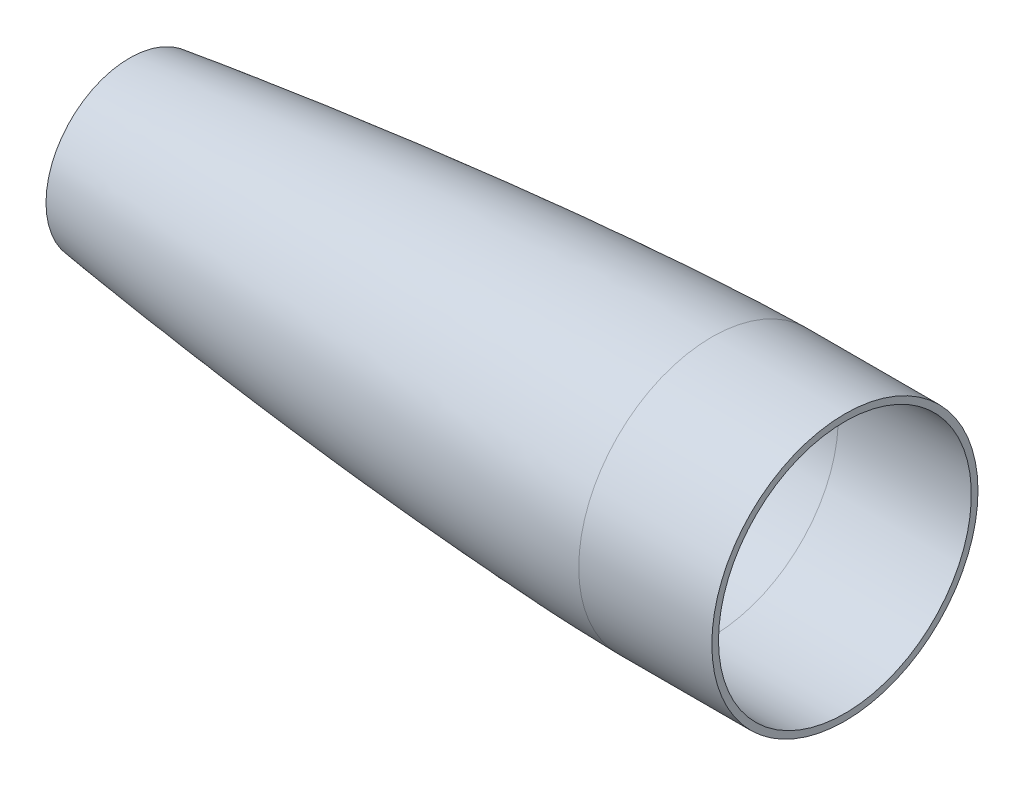
SolidWorks part; units mm, degrees
ref_plane "Front Plane" through (0, 0, 0) normal (0, 0, 1) x (1, 0, 0)
ref_plane "Top Plane" through (0, 0, 0) normal (0, 1, 0) x (1, 0, 0)
ref_plane "Right Plane" through (0, 0, 0) normal (1, 0, 0) x (0, 0, -1)
curve "Curve1"
  spline degree 3 poles (0, 0, 0) (0.3239, 0.2563, 0) (0.9404, 0.7441, 0) (1.9928, 1.2129, 0) (2.9928, 1.6503, 0) (3.9962, 2.0429, 0) (4.997, 2.4136, 0) (5.9977, 2.765, 0) (6.9982, 3.102, 0) (7.9985, 3.4266, 0) (8.9987, 3.7409, 0) (9.9989, 4.0463, 0) (10.999, 4.3437, 0) (11.9992, 4.6341, 0) (12.9993, 4.9182, 0) (13.9993, 5.1965, 0) (14.9994, 5.4695, 0) (15.9994, 5.7378, 0) (16.9995, 6.0015, 0) (17.9995, 6.261, 0) (18.9996, 6.5167, 0) (19.9996, 6.7687, 0) (20.9996, 7.0173, 0) (21.9996, 7.2626, 0) (22.9997, 7.5048, 0) (23.9997, 7.7441, 0) (24.9997, 7.9806, 0) (25.9997, 8.2145, 0) (26.9997, 8.4458, 0) (27.9997, 8.6747, 0) (28.9998, 8.9012, 0) (29.9998, 9.1256, 0) (30.9998, 9.3477, 0) (31.9998, 9.5678, 0) (32.9998, 9.7859, 0) (33.9998, 10.0021, 0) (34.9998, 10.2164, 0) (35.9998, 10.4289, 0) (36.9998, 10.6396, 0) (37.9998, 10.8486, 0) (38.9998, 11.056, 0) (39.9998, 11.2617, 0) (40.9999, 11.4659, 0) (41.9999, 11.6686, 0) (42.9999, 11.8698, 0) (43.9999, 12.0696, 0) (44.9999, 12.2679, 0) (45.9999, 12.4649, 0) (46.9999, 12.6605, 0) (47.9999, 12.8548, 0) (48.9999, 13.0478, 0) (49.9999, 13.2396, 0) (50.9999, 13.4301, 0) (51.9999, 13.6194, 0) (52.9999, 13.8076, 0) (53.9999, 13.9946, 0) (54.9999, 14.1804, 0) (55.9999, 14.3652, 0) (56.9999, 14.5488, 0) (57.9999, 14.7314, 0) (58.9999, 14.9129, 0) (59.9999, 15.0934, 0) (60.9999, 15.2728, 0) (61.9999, 15.4513, 0) (62.9999, 15.6288, 0) (63.9999, 15.8052, 0) (64.9999, 15.9808, 0) (65.9999, 16.1554, 0) (66.9999, 16.329, 0) (67.9999, 16.5018, 0) (68.9999, 16.6736, 0) (69.9999, 16.8445, 0) (70.9999, 17.0146, 0) (71.9999, 17.1838, 0) (72.9999, 17.3522, 0) (73.9999, 17.5197, 0) (74.9999, 17.6863, 0) (75.9999, 17.8522, 0) (76.9999, 18.0172, 0) (77.9999, 18.1814, 0) (78.9999, 18.3449, 0) (79.9999, 18.5075, 0) (80.9999, 18.6694, 0) (81.9999, 18.8305, 0) (82.9999, 18.9908, 0) (83.9999, 19.1504, 0) (84.9999, 19.3092, 0) (85.9999, 19.4673, 0) (86.9999, 19.6247, 0) (87.9999, 19.7814, 0) (88.9999, 19.9373, 0) (89.9999, 20.0925, 0) (90.9999, 20.2471, 0) (91.9999, 20.4009, 0) (92.9999, 20.554, 0) (93.9999, 20.7065, 0) (95, 20.8583, 0) (96, 21.0094, 0) (97, 21.1598, 0) (98, 21.3096, 0) (99, 21.4587, 0) (100, 21.6072, 0) (101, 21.755, 0) (102, 21.9022, 0) (103, 22.0488, 0) (104, 22.1947, 0) (105, 22.34, 0) (106, 22.4846, 0) (107, 22.6287, 0) (108, 22.7721, 0) (109, 22.915, 0) (110, 23.0572, 0) (111, 23.1988, 0) (112, 23.3398, 0) (113, 23.4803, 0) (114, 23.6201, 0) (115, 23.7594, 0) (116, 23.898, 0) (117, 24.0361, 0) (118, 24.1736, 0) (119, 24.3106, 0) (120, 24.4469, 0) (121, 24.5827, 0) (122, 24.718, 0) (123, 24.8526, 0) (124, 24.9867, 0) (125, 25.1203, 0) (126, 25.2533, 0) (127, 25.3857, 0) (128, 25.5176, 0) (129, 25.649, 0) (130, 25.7798, 0) (131, 25.91, 0) (132, 26.0397, 0) (133, 26.1689, 0) (134, 26.2975, 0) (135, 26.4257, 0) (136, 26.5532, 0) (137, 26.6803, 0) (138, 26.8068, 0) (139, 26.9328, 0) (140, 27.0582, 0) (141, 27.1832, 0) (142, 27.3076, 0) (143, 27.4315, 0) (144, 27.5549, 0) (145, 27.6777, 0) (146, 27.8001, 0) (147, 27.9219, 0) (148, 28.0432, 0) (149, 28.1641, 0) (150, 28.2844, 0) (151, 28.4041, 0) (152, 28.5234, 0) (153, 28.6422, 0) (154, 28.7605, 0) (155, 28.8782, 0) (156, 28.9955, 0) (157, 29.1122, 0) (158, 29.2285, 0) (159, 29.3442, 0) (160, 29.4595, 0) (161, 29.5742, 0) (162, 29.6885, 0) (163, 29.8022, 0) (164, 29.9155, 0) (165, 30.0282, 0) (166, 30.1405, 0) (167, 30.2522, 0) (168, 30.3635, 0) (169, 30.4743, 0) (170, 30.5845, 0) (171, 30.6943, 0) (172, 30.8036, 0) (173, 30.9124, 0) (174, 31.0207, 0) (175, 31.1285, 0) (176, 31.2358, 0) (177, 31.3426, 0) (178, 31.4489, 0) (179, 31.5547, 0) (180, 31.66, 0) (181, 31.7649, 0) (182, 31.8692, 0) (183, 31.973, 0) (184, 32.0764, 0) (185, 32.1792, 0) (186, 32.2816, 0) (187, 32.3834, 0) (188, 32.4848, 0) (189, 32.5856, 0) (190, 32.686, 0) (191, 32.7859, 0) (192, 32.8852, 0) (193, 32.9841, 0) (194, 33.0825, 0) (195, 33.1803, 0) (196, 33.2777, 0) (197, 33.3746, 0) (198, 33.4709, 0) (199, 33.5668, 0) (200, 33.6621, 0) (201, 33.757, 0) (202, 33.8513, 0) (203, 33.9451, 0) (204, 34.0385, 0) (205, 34.1313, 0) (206, 34.2236, 0) (207, 34.3153, 0) (208, 34.4066, 0) (209, 34.4973, 0) (210, 34.5876, 0) (211, 34.6773, 0) (212, 34.7665, 0) (213, 34.8551, 0) (214, 34.9433, 0) (215, 35.0309, 0) (216, 35.118, 0) (217, 35.2045, 0) (218, 35.2906, 0) (219, 35.3761, 0) (220, 35.461, 0) (221, 35.5454, 0) (222, 35.6293, 0) (223, 35.7126, 0) (224, 35.7954, 0) (225, 35.8776, 0) (226, 35.9593, 0) (227, 36.0404, 0) (228, 36.121, 0) (229, 36.201, 0) (230, 36.2805, 0) (231, 36.3594, 0) (232, 36.4377, 0) (233, 36.5154, 0) (234, 36.5926, 0) (235, 36.6692, 0) (236, 36.7452, 0) (237, 36.8206, 0) (238, 36.8954, 0) (239, 36.9696, 0) (240, 37.0432, 0) (241, 37.1163, 0) (242, 37.1887, 0) (243, 37.2605, 0) (244, 37.3317, 0) (245, 37.4022, 0) (246, 37.4722, 0) (247, 37.5415, 0) (248, 37.6102, 0) (249, 37.6782, 0) (250, 37.7455, 0) (251, 37.8123, 0) (252, 37.8783, 0) (253, 37.9437, 0) (254, 38.0084, 0) (255, 38.0725, 0) (256, 38.1358, 0) (257, 38.1985, 0) (258, 38.2604, 0) (259, 38.3216, 0) (260, 38.3821, 0) (261, 38.4419, 0) (262, 38.5009, 0) (263, 38.5592, 0) (264, 38.6168, 0) (265, 38.6735, 0) (266, 38.7295, 0) (267, 38.7847, 0) (268, 38.8391, 0) (269, 38.8926, 0) (270, 38.9454, 0) (271, 38.9972, 0) (272, 39.0483, 0) (273, 39.0984, 0) (274, 39.1477, 0) (275, 39.196, 0) (276, 39.2434, 0) (277, 39.2899, 0) (278, 39.3354, 0) (279, 39.3799, 0) (280, 39.4234, 0) (281, 39.4658, 0) (282, 39.5072, 0) (283, 39.5475, 0) (284, 39.5866, 0) (285, 39.6246, 0) (286, 39.6613, 0) (287, 39.6968, 0) (288, 39.731, 0) (289, 39.7638, 0) (290, 39.7952, 0) (291, 39.8251, 0) (292, 39.8533, 0) (293, 39.88, 0) (294, 39.9048, 0) (295, 39.9276, 0) (296, 39.9483, 0) (297, 39.9666, 0) (298, 39.982, 0) (299, 39.9947, 0) (299.6667, 39.9982, 0) (300, 40, 0) knots 0 0 0 0 0.004064 0.007736 0.011323 0.014865 0.018378 0.021871 0.025347 0.028811 0.032264 0.035709 0.039146 0.042576 0.046001 0.04942 0.052835 0.056246 0.059653 0.063056 0.066457 0.069854 0.073248 0.07664 0.08003 0.083417 0.086802 0.090186 0.093567 0.096946 0.100324 0.1037 0.107075 0.110448 0.11382 0.11719 0.120559 0.123927 0.127294 0.130659 0.134023 0.137387 0.140749 0.14411 0.14747 0.15083 0.154188 0.157546 0.160902 0.164258 0.167613 0.170968 0.174321 0.177674 0.181026 0.184378 0.187728 0.191078 0.194428 0.197776 0.201124 0.204472 0.207819 0.211165 0.214511 0.217856 0.221201 0.224545 0.227888 0.231231 0.234574 0.237916 0.241258 0.244599 0.247939 0.251279 0.254619 0.257958 0.261297 0.264636 0.267974 0.271311 0.274648 0.277985 0.281321 0.284657 0.287993 0.291328 0.294663 0.297997 0.301331 0.304665 0.307999 0.311332 0.314664 0.317997 0.321329 0.32466 0.327992 0.331323 0.334653 0.337984 0.341314 0.344643 0.347973 0.351302 0.354631 0.35796 0.361288 0.364616 0.367943 0.371271 0.374598 0.377925 0.381251 0.384578 0.387904 0.39123 0.394555 0.39788 0.401205 0.40453 0.407855 0.411179 0.414503 0.417827 0.42115 0.424474 0.427797 0.431119 0.434442 0.437764 0.441086 0.444408 0.44773 0.451051 0.454372 0.457693 0.461014 0.464335 0.467655 0.470975 0.474295 0.477615 0.480934 0.484253 0.487572 0.490891 0.49421 0.497528 0.500846 0.504165 0.507482 0.5108 0.514117 0.517435 0.520752 0.524068 0.527385 0.530702 0.534018 0.537334 0.54065 0.543965 0.547281 0.550596 0.553911 0.557226 0.560541 0.563856 0.56717 0.570484 0.573799 0.577112 0.580426 0.58374 0.587053 0.590366 0.593679 0.596992 0.600305 0.603617 0.606929 0.610242 0.613554 0.616865 0.620177 0.623489 0.6268 0.630111 0.633422 0.636733 0.640043 0.643354 0.646664 0.649974 0.653284 0.656594 0.659904 0.663213 0.666523 0.669832 0.673141 0.67645 0.679759 0.683067 0.686376 0.689684 0.692992 0.6963 0.699608 0.702916 0.706223 0.70953 0.712838 0.716145 0.719452 0.722758 0.726065 0.729371 0.732678 0.735984 0.73929 0.742596 0.745901 0.749207 0.752512 0.755817 0.759122 0.762427 0.765732 0.769037 0.772341 0.775646 0.77895 0.782254 0.785558 0.788862 0.792165 0.795469 0.798772 0.802075 0.805378 0.808681 0.811984 0.815287 0.818589 0.821891 0.825193 0.828496 0.831797 0.835099 0.838401 0.841702 0.845003 0.848305 0.851606 0.854907 0.858207 0.861508 0.864808 0.868109 0.871409 0.874709 0.878009 0.881308 0.884608 0.887907 0.891207 0.894506 0.897805 0.901104 0.904402 0.907701 0.910999 0.914297 0.917596 0.920894 0.924191 0.927489 0.930787 0.934084 0.937381 0.940678 0.943975 0.947272 0.950569 0.953865 0.957161 0.960458 0.963754 0.96705 0.970345 0.973641 0.976936 0.980232 0.983527 0.986822 0.990117 0.993411 0.996706 1 1 1 1
sketch "Sketch2" plane through (0, 0, 0) normal (0, 0, 1) x (1, 0, 0)
  line L0 (0, 0) -> (129.646, 0) construction
  line L2 (300, 40) -> (300.0106, 38) construction
  line L3 (0, 0) -> (4.2671, 0)
  line L4 (300, 40) -> (340, 40)
  line L5 (340, 40) -> (340, 38)
  line L6 (340, 38) -> (300.0106, 38)
  line L7 (125, 25.1202) -> (125, 0)
  line L8 (125, 0) -> (127, 0)
  line L9 (127, 0) -> (127, 23.3682)
  spline S0 degree 3 poles (-1078.6787, 1683.532) (10.1579, -68.1289) (-11.6434, -4.8611) (1.9928, 1.2129) (2.9928, 1.6503) (3.9962, 2.0429) (4.997, 2.4136) (5.9977, 2.765) (6.9982, 3.102) (7.9985, 3.4266) (8.9987, 3.7409) (9.9989, 4.0463) (10.999, 4.3437) (11.9992, 4.6341) (12.9993, 4.9182) (13.9993, 5.1965) (14.9994, 5.4695) (15.9994, 5.7378) (17.3322, 6.0892) (18.9983, 6.5182) (20.9985, 7.0186) (22.9987, 7.506) (24.9988, 7.9817) (26.9989, 8.4468) (28.999, 8.9022) (31.332, 9.4229) (33.9983, 10.0043) (36.9985, 10.6416) (39.9986, 11.2636) (42.9987, 11.8715) (46.3318, 12.5325) (49.9982, 13.2423) (53.9984, 13.9971) (57.9985, 14.7338) (62.3316, 15.5134) (66.9981, 16.3324) (71.9982, 17.187) (77.3314, 18.0757) (82.9979, 18.9949) (88.9981, 19.9411) (95.3312, 20.913) (101.9978, 21.907) (108.9979, 22.9195) (116.3311, 23.9492) (123.9977, 24.9923) (131.9978, 26.0451) (140.331, 27.1059) (148.9975, 28.1706) (157.9977, 29.2349) (166.9978, 30.2586) (175.9979, 31.2421) (184.998, 32.1856) (193.998, 33.089) (202.665, 33.9198) (210.9985, 34.6826) (218.6654, 35.3525) (225.9989, 35.9637) (232.9989, 36.5199) (239.6657, 37.0229) (245.9992, 37.4758) (251.666, 37.8596) (256.9995, 38.2012) (261.6662, 38.4837) (265.9996, 38.7315) (269.9996, 38.9474) (273.6664, 39.1331) (276.9998, 39.2912) (279.9998, 39.4248) (282.6665, 39.5352) (284.9999, 39.6252) (286.9999, 39.6975) (288.9999, 39.7645) (290.6666, 39.8156) (292.3333, 39.8628) (293.6666, 39.8971) (295, 39.9276) (296, 39.9483) (297, 39.9666) (298, 39.982) (338.0832, 40.4918) (377.984, 23.3924) (400.1416, 2036.2438) knots -0.135384 -0.135384 -0.135384 -0.135384 0.004064 0.007736 0.011323 0.014865 0.018378 0.021871 0.025347 0.028811 0.032264 0.035709 0.039146 0.042576 0.046001 0.04942 0.052835 0.056246 0.059653 0.066457 0.073248 0.08003 0.086802 0.093567 0.100324 0.107075 0.11719 0.127294 0.137387 0.14747 0.157546 0.170968 0.184378 0.197776 0.211165 0.227888 0.244599 0.261297 0.281321 0.301331 0.321329 0.344643 0.367943 0.39123 0.417827 0.444408 0.470975 0.500846 0.530702 0.560541 0.590366 0.620177 0.649974 0.679759 0.706223 0.732678 0.755817 0.77895 0.802075 0.821891 0.841702 0.858207 0.874709 0.887907 0.901104 0.914297 0.924191 0.934084 0.943975 0.950569 0.957161 0.963754 0.970345 0.973641 0.980232 0.983527 0.986822 0.990117 0.993411 0.996706 1.38628 1.38628 1.38628 1.38628 only from (0, 0) to (300, 40) construction
  spline S1 degree 3 poles (0, 0) (0.3239, 0.2563) (0.9404, 0.7441) (1.9928, 1.2129) (2.9928, 1.6503) (3.9962, 2.0429) (4.997, 2.4136) (5.9977, 2.765) (6.9982, 3.102) (7.9985, 3.4266) (8.9987, 3.7409) (9.9989, 4.0463) (10.999, 4.3437) (11.9992, 4.6341) (12.9993, 4.9182) (13.9993, 5.1965) (14.9994, 5.4695) (15.9994, 5.7378) (17.3322, 6.0892) (18.9983, 6.5182) (20.9985, 7.0186) (22.9987, 7.506) (24.9988, 7.9817) (26.9989, 8.4468) (28.999, 8.9022) (31.332, 9.4229) (33.9983, 10.0043) (36.9985, 10.6416) (39.9986, 11.2636) (42.9987, 11.8715) (46.3318, 12.5325) (49.9982, 13.2423) (53.9984, 13.9971) (57.9985, 14.7338) (62.3316, 15.5134) (66.9981, 16.3324) (71.9982, 17.187) (77.3314, 18.0757) (82.9979, 18.9949) (88.9981, 19.9411) (95.3312, 20.913) (101.9978, 21.907) (108.9979, 22.9195) (116.3311, 23.9492) (123.9977, 24.9923) (131.9978, 26.0451) (140.331, 27.1059) (148.9975, 28.1706) (157.9977, 29.2349) (166.9978, 30.2586) (175.9979, 31.2421) (184.998, 32.1856) (193.998, 33.089) (202.665, 33.9198) (210.9985, 34.6826) (218.6654, 35.3525) (225.9989, 35.9637) (232.9989, 36.5199) (239.6657, 37.0229) (245.9992, 37.4758) (251.666, 37.8596) (256.9995, 38.2012) (261.6662, 38.4837) (265.9996, 38.7315) (269.9996, 38.9474) (273.6664, 39.1331) (276.9998, 39.2912) (279.9998, 39.4248) (282.6665, 39.5352) (284.9999, 39.6252) (286.9999, 39.6975) (288.9999, 39.7645) (290.6666, 39.8156) (292.3333, 39.8628) (293.6666, 39.8971) (295, 39.9276) (296, 39.9483) (297, 39.9666) (298, 39.982) (299, 39.9947) (299.6667, 39.9982) (300, 40) knots 0 0 0 0 0.004064 0.007736 0.011323 0.014865 0.018378 0.021871 0.025347 0.028811 0.032264 0.035709 0.039146 0.042576 0.046001 0.04942 0.052835 0.056246 0.059653 0.066457 0.073248 0.08003 0.086802 0.093567 0.100324 0.107075 0.11719 0.127294 0.137387 0.14747 0.157546 0.170968 0.184378 0.197776 0.211165 0.227888 0.244599 0.261297 0.281321 0.301331 0.321329 0.344643 0.367943 0.39123 0.417827 0.444408 0.470975 0.500846 0.530702 0.560541 0.590366 0.620177 0.649974 0.679759 0.706223 0.732678 0.755817 0.77895 0.802075 0.821891 0.841702 0.858207 0.874709 0.887907 0.901104 0.914297 0.924191 0.934084 0.943975 0.950569 0.957161 0.963754 0.970345 0.973641 0.980232 0.983527 0.986822 0.990117 0.993411 0.996706 1 1 1 1
  spline S2 degree 1 poles (1.241, -1.5684) (300.0106, 38) knots 0 0 1 1 construction
  spline S3 degree 3 poles (1.241, -1.5684) (1.3807, -1.4578) (1.6881, -1.216) (1.9997, -1.0018) (2.3173, -0.8331) (2.8232, -0.6074) (3.3618, -0.3714) (3.7849, -0.1929) (4.1325, -0.0528) (4.4813, 0.0842) (5.4558, 0.4556) (7.0834, 1.031) (10.037, 1.984) (13.7867, 3.0797) (18.3317, 4.2942) (22.9057, 5.4346) (29.0314, 6.8774) (36.7255, 8.5622) (45.9958, 10.445) (55.293, 12.2166) (64.6107, 13.8956) (77.0563, 16.0277) (92.6469, 18.5165) (108.7755, 20.885) (121.7966, 22.6819) (134.3222, 24.3389) (155.7568, 27.0201) (186.6476, 30.4535) (218.1037, 33.3675) (243.2964, 35.3133) (262.2047, 36.5525) (277.9645, 37.3696) (290.5821, 37.831) (296.865, 37.9834) (300.0106, 38) knots 0 0 0 0 0.001953 0.003906 0.005859 0.007812 0.009766 0.011719 0.012737 0.013714 0.015625 0.023438 0.03125 0.046875 0.0625 0.078125 0.09375 0.125 0.15625 0.1875 0.21875 0.25 0.3125 0.375 0.4113 0.44255 0.5 0.625 0.75 0.8125 0.875 0.9375 0.96875 1 1 1 1 only from (4.2671, 0) to (300.0106, 38)
  dimension "D2" = 40
  dimension "D3" = 2
  dimension "D4" = 175
  dimension "D1" = 2
revolve "Revolve1" add sketch "Sketch2" angle 360 about L0 region at (212.335, 34.5796, 0) region at (126.0019, 11.6179, 0)
sketch "Sketch3" plane through (125, 0, 0) normal (-1, 0, 0) x (0, 0, 1)
  circle A2 centre (0, 0) radius 3.1
  dimension "D1" = 6.2
extrude "Cut-Extrude1" cut sketch "Sketch3" against normal through all
